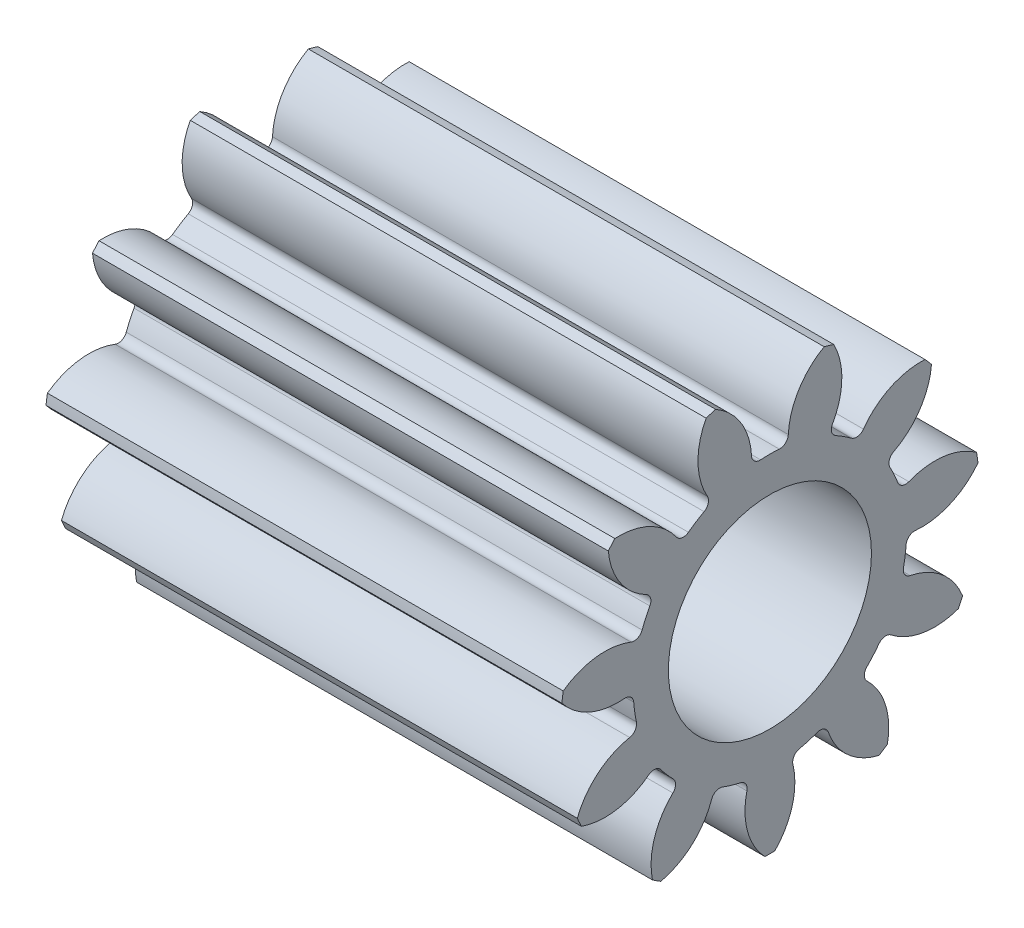
SolidWorks part; units mm, degrees
ref_plane "Plane1" through (0, 0, 0) normal (0, 0, 1) x (1, 0, 0)
ref_plane "Plane2" through (0, 0, 0) normal (0, 1, 0) x (1, 0, 0)
ref_plane "Plane3" through (0, 0, 0) normal (1, 0, 0) x (0, 0, -1)
other "Configuration Table"
sketch "HoldingSke" plane through (0, 0, 0) normal (0, 1, 0) x (1, 0, 0)
  line L0 (0, 0) -> (797.8666, -155.0896)
  line L1 (-15, 0) -> (100, 0) construction
  line L2 (0, 0) -> (-2.1039, 2.3779)
  line L3 (0, 0) -> (-11.863, 4.5341)
  line L4 (0, 0) -> (8.4773, 1.6478)
  line L5 (0, 0) -> (-47.5972, -17.7524)
  line L6 (0, 0) -> (-10.5278, -7.1032)
  line L7 (-2.1039, 2.3779) -> (8.8308, 51.9873)
  line L8 (-76.2, 54.61) -> (-75.184, 54.61)
  line L9 (-71.009, 38.7566) -> (-53.1078, 45.2721)
  line L10 (-76.2, 71.12) -> (104.1128, 71.12)
  line L11 (0, 0) -> (-12.7, 0)
  line L12 (-76.2, 101.6) -> (-76.1716, 101.6)
  line L13 (24.9733, 27.94) -> (52.9518, 28.4284)
  line L14 (24.9733, 27.94) -> (25.0241, 27.9398)
  line L15 (24.9733, 27.94) -> (100.4021, 29.52)
  circle A0 centre (0, 0) radius 0.3969
  circle A1 centre (0, 0) radius 3.3623
  circle A2 centre (0, 0) radius 38.1
  circle A3 centre (0, 0) radius 0.3969
  dimension "MHD" = 6.7246
  dimension "Hub_dia" = 76.2
  dimension "Bore" = 0.7937
  dimension "MBD" = 0.7937
  dimension "Num_teeth" = 11
  dimension "Pitch" = 812.8
  dimension "Overall_len" = 50.8
  dimension "Show_teeth" = 11
  dimension "Thickness" = 12.7
  dimension "OAL" = 50.8003
  dimension "T_dim" = 1.016
  dimension "Ap" = 20
  dimension "H" = 19.05
  dimension "Pitch_radius" = 180.3128
  dimension "Width" = 12.7
  dimension "Backlash" = 0.0284
  dimension "Addendum_fac" = 1
  dimension "Dedendum_fac" = 1.2
  dimension "Clearance_fac" = 0.2
  dimension "Dedendum_add" = 0.0508
sketch "BasProSke" plane through (0, 0, 0) normal (0, 1, 0) x (1, 0, 0)
  line L0 (-10, 0) -> (60, 0) construction
  line L1 (0, 0) -> (0, 5.1594)
  line L2 (0, 0) -> (12.7, 0)
  line L3 (12.7, 0) -> (12.7, 5.1594)
  line L4 (12.7, 5.1594) -> (0, 5.1594)
  dimension "Thickness" = 12.7
  dimension "Diameter" = 10.3187
revolve "Base-Revolve" add sketch "BasProSke" angle 360 about L0
sketch "TooCutSke" plane through (0, 0, 0) normal (1, 0, 0) x (0, 0, -1)
  line L1 (0, 0) -> (0, 107) construction
  line L2 (0, 0) -> (-0.671, 4.3138) construction
  line L3 (0, 0) -> (-2.4387, 8.3055) construction
  line L4 (-0.671, 4.3138) -> (-1.2194, 4.1527) construction
  arc A0 (0.4557, 3.3313) -> (-0.4557, 3.3313) centre (0, 0) ccw
  arc A1 (1.3674, 5.0012) -> (-1.3674, 5.0012) centre (0, 0) ccw
  circle A2 centre (0, 0) radius 4.3656 construction
  circle A3 centre (0, 0) radius 4.1023 construction
  arc A4 (-0.4557, 3.3313) -> (-1.3674, 5.0012) centre (-2.1969, 3.4645) ccw
  arc A5 (1.3674, 5.0012) -> (0.4557, 3.3313) centre (2.1969, 3.4645) ccw
  dimension "Root_dia" = 6.7246
  dimension "Overcut_dia" = 10.3696
  dimension "Pitch_dia" = 8.7312
  dimension "Base_dia" = 8.2047
  dimension "Flank_rad" = 1.7463
  dimension "Half_ang" = 16.364
  dimension "Half_CT" = 0.5715
extrude "ToothCut" cut sketch "TooCutSke" along normal through all
fillet "Breaks" [suppressed] radius 0.0159 tangent propagation no
fillet "RootFillets" radius 0.2095 2 edges at (6.35, 3.3313, -0.4557) (6.35, 3.3313, 0.4557)
pattern_circular "TeethCuts" count 11 every 32.727 about axis through (-10, 0, 0) along (1, 0, 0) of "ToothCut", "RootFillets", "Breaks"
sketch "HubNeaOneSke" plane through (0, 0, 0) normal (-1, 0, 0) x (0, 0, 1)
  circle A0 centre (0, 0) radius 3.3623
  dimension "Diameter" = 6.7246
extrude "HubNearOne" [suppressed] add sketch "HubNeaOneSke" along normal blind 38.1003
sketch "HubNeaBotSke" plane through (0, 0, 0) normal (-1, 0, 0) x (0, 0, 1)
  circle A0 centre (0, 0) radius 3.3623
  dimension "Diameter" = 6.7246
extrude "HubNearBoth" [suppressed] add sketch "HubNeaBotSke" along normal blind 19.0501
ref_plane "FarPln" through (12.7, 0, 0) normal (1, 0, 0) x (0, 0, -1)
sketch "HubFarSke" plane through (12.7, 0, 0) normal (1, 0, 0) x (0, 0, -1)
  circle A0 centre (0, 0) radius 3.3623
  dimension "Diameter" = 6.7246
extrude "HubFar" [suppressed] add sketch "HubFarSke" along normal blind 19.0501
sketch "BorSke" plane through (0, 0, 0) normal (1, 0, 0) x (0, 0, -1)
  circle A0 centre (0, 0) radius 0.3969
  dimension "Diameter" = 0.7937
extrude "Bore" [suppressed] cut sketch "BorSke" along normal mid plane 101.6005
sketch "KeySke" plane through (0, 0, 0) normal (1, 0, 0) x (0, 0, -1)
  line L0 (-0.127, 0) -> (-0.127, 0.6191)
  line L1 (-0.127, 0.6191) -> (0.127, 0.6191)
  line L2 (0.127, 0.6191) -> (0.127, 0)
  line L3 (0, 0) -> (0, 34) construction
  line L4 (-0.127, 0) -> (0.127, 0)
  dimension "Offset" = 0.6191
  dimension "Width" = 0.254
extrude "Keyway" [suppressed] cut sketch "KeySke" along normal mid plane 101.6005
pattern_circular "Keyway2" [suppressed] count 2 every 90 about axis through (-10, 0, 0) along (1, 0, 0) reverse direction yes
sketch "Sketch1" plane through (12.7, 0, 0) normal (1, 0, 0) x (0, 0, -1)
  circle A0 centre (0, 0) radius 2.5
  dimension "D1" = 5
extrude "Cut-Extrude1" cut sketch "Sketch1" against normal up to next
equation "' \"Pitch@HoldingSke\" = 4"
equation "' \"Num_teeth@HoldingSke\" = 12"
equation "' \"Ap@HoldingSke\" =  20"
equation "' \"Ap@HoldingSke\" = 20"
equation "' \"Width@HoldingSke\" = 0.5"
equation "' \"Hub_dia@HoldingSke\"= 1"
equation "' \"Hub_dia@HoldingSke\" = 1"
equation "' \"Overall_len@HoldingSke\" = 1.0"
equation "' \"Bore@HoldingSke\" = 0.75"
equation "' \"T_dim@HoldingSke\" = 0.85"
equation "' \"Width@KeySke\" = 0.25"
equation "' \"Show_teeth@HoldingSke\" = 13"
equation "' \"Backlash@HoldingSke\" = 0.009"
equation "' \"Addendum_fac@HoldingSke\" = 1.0"
equation "' \"Dedendum_fac@HoldingSke\" = 1.25"
equation "' \"Dedendum_add@HoldingSke\" = 0.00005"
equation "' \"Clearance_fac@HoldingSke\" = 0.25"
equation "' \"Pitch@HoldingSke\" = 0.5"
equation "' \"Num_teeth@HoldingSke\" = 23"
equation "' \"Show_teeth@HoldingSke\" = 23"
equation "' \"Backlash@HoldingSke\" = 0.0375"
equation "\"Overcut_dia@TooCutSke\" = (\"Num_teeth@HoldingSke\" + 2 * \"Addendum_fac@HoldingSke\") / \"Pitch@HoldingSke\" + 0.002"
equation "\"Pitch_dia@TooCutSke\" = \"Num_teeth@HoldingSke\" / \"Pitch@HoldingSke\""
equation "\"Base_dia@TooCutSke\" = \"Num_teeth@HoldingSke\" / \"Pitch@HoldingSke\" * cos((\"Ap@HoldingSke\"  * 3.14159265 / 180))"
equation "\"Root_dia@TooCutSke\" = (\"Num_teeth@HoldingSke\" + 2) / \"Pitch@HoldingSke\" - 2 * (\"Addendum_fac@HoldingSke\" + \"Dedendum_fac@HoldingSke\") / \"Pitch@HoldingSke\" - \"Dedendum_add@HoldingSke\" * 2"
equation "\"Half_ang@TooCutSke\" = 180 / \"Num_teeth@HoldingSke\""
equation "\"Half_CT@TooCutSke\" = \"Num_teeth@HoldingSke\" / \"Pitch@HoldingSke\" * sin((3.14159265 / 2 / \"Num_teeth@HoldingSke\")) / 2 - 7 * \"Backlash@HoldingSke\" / 4"
equation "\"Flank_rad@TooCutSke\" = \"Num_teeth@HoldingSke\" / \"Pitch@HoldingSke\" / 5"
equation "\"Radius@RootFillets\" = \"Clearance_fac@HoldingSke\" / \"Pitch@HoldingSke\" + \"Dedendum_add@HoldingSke\""
equation "\"Break_rad@Breaks\" = 0.02 / \"Pitch@HoldingSke\""
equation "\"Thickness@HoldingSke\" = \"Width@HoldingSke\""
equation "\"OAL@HoldingSke\" = \"Thickness@HoldingSke\""
equation "\"MHD@HoldingSke\" = (\"Num_teeth@HoldingSke\" + 2) / \"Pitch@HoldingSke\" - 2 * (\"Addendum_fac@HoldingSke\" + \"Dedendum_fac@HoldingSke\")  / \"Pitch@HoldingSke\" - \"Dedendum_add@HoldingSke\" * 2"
equation "\"MBD@HoldingSke\" = (\"Num_teeth@HoldingSke\" + 2) / \"Pitch@HoldingSke\" - 2 * (\"Addendum_fac@HoldingSke\" + \"Dedendum_fac@HoldingSke\")  / \"Pitch@HoldingSke\" - \"Dedendum_add@HoldingSke\" * 2 - 0.002"
equation "\"MHD@HoldingSke\" = ((sgn( \"MHD@HoldingSke\" - \"Hub_dia@HoldingSke\" )-1)*( \"MHD@HoldingSke\" - \"Hub_dia@HoldingSke\" ))/-2+ \"Hub_dia@HoldingSke\""
equation "\"MBD@HoldingSke\" = ((sgn( \"MBD@HoldingSke\" - \"Bore@HoldingSke\" )-1)*( \"MBD@HoldingSke\" - \"Bore@HoldingSke\" ))/-2+ \"Bore@HoldingSke\""
equation "\"OAL@HoldingSke\" = ((sgn( \"OAL@HoldingSke\" - \"Overall_len@HoldingSke\" )+1)*( \"OAL@HoldingSke\" - \"Overall_len@HoldingSke\" ))/2 + \"Overall_len@HoldingSke\" + 0.000002"
equation "\"Num_teeth@TeethCuts\" = int( \"Show_teeth@HoldingSke\" ) + 1"
equation "\"Num_teeth@TeethCuts\" = ((sgn( \"Num_teeth@TeethCuts\" - \"Num_teeth@HoldingSke\" )-1)*( \"Num_teeth@TeethCuts\" - \"Num_teeth@HoldingSke\" ))/-2+ \"Num_teeth@HoldingSke\""
equation "\"Num_teeth@TeethCuts\" = ((sgn( \"Num_teeth@TeethCuts\" - 2.0)+1)*( \"Num_teeth@TeethCuts\" - 2.0))/2 +2.0"
equation "\"Angle@TeethCuts\" = 360.0 / \"Num_teeth@HoldingSke\""
equation "\"Diameter@BasProSke\" = (\"Num_teeth@HoldingSke\" + 2 * \"Addendum_fac@HoldingSke\") / \"Pitch@HoldingSke\""
equation "\"Thickness@BasProSke\"  = \"Thickness@HoldingSke\""
equation "' \"Fillet_rad@BasProSke\" =  \"Thickness@HoldingSke\" * 0.05"
equation "' \"Fillet_rad@BasProSke\" = \"Thickness@HoldingSke\" * 0.05"
equation "\"MHD@HoldingSke\" = ((sgn( \"MHD@HoldingSke\" - \"Root_dia@TooCutSke\" )-1)*( \"MHD@HoldingSke\" - \"Root_dia@TooCutSke\" ))/-2+ \"Root_dia@TooCutSke\""
equation "\"Diameter@HubNeaOneSke\" = \"MHD@HoldingSke\""
equation "\"Length@HubNearOne\" = \"OAL@HoldingSke\" - \"Thickness@BasProSke\""
equation "\"Diameter@HubNeaBotSke\" = \"MHD@HoldingSke\""
equation "\"Length@HubNearBoth\" = ( \"OAL@HoldingSke\" - \"Thickness@BasProSke\" ) / 2.0"
equation "\"Thickness@FarPln\" = \"Thickness@BasProSke\""
equation "\"Diameter@HubFarSke\" = \"MHD@HoldingSke\""
equation "\"Length@HubFar\" = ( \"OAL@HoldingSke\" - \"Thickness@BasProSke\" ) / 2.0"
equation "\"Diameter@BorSke\" = \"MBD@HoldingSke\""
equation "\"D1@Bore\" = \"OAL@HoldingSke\" * 2.0"
equation "\"D1@Keyway\" = \"OAL@HoldingSke\" * 2.0"
equation "\"Offset@KeySke\" = \"T_dim@HoldingSke\" - \"MBD@HoldingSke\" / 2.0"
equation "\"D1@Sketch1\"=5mm"
